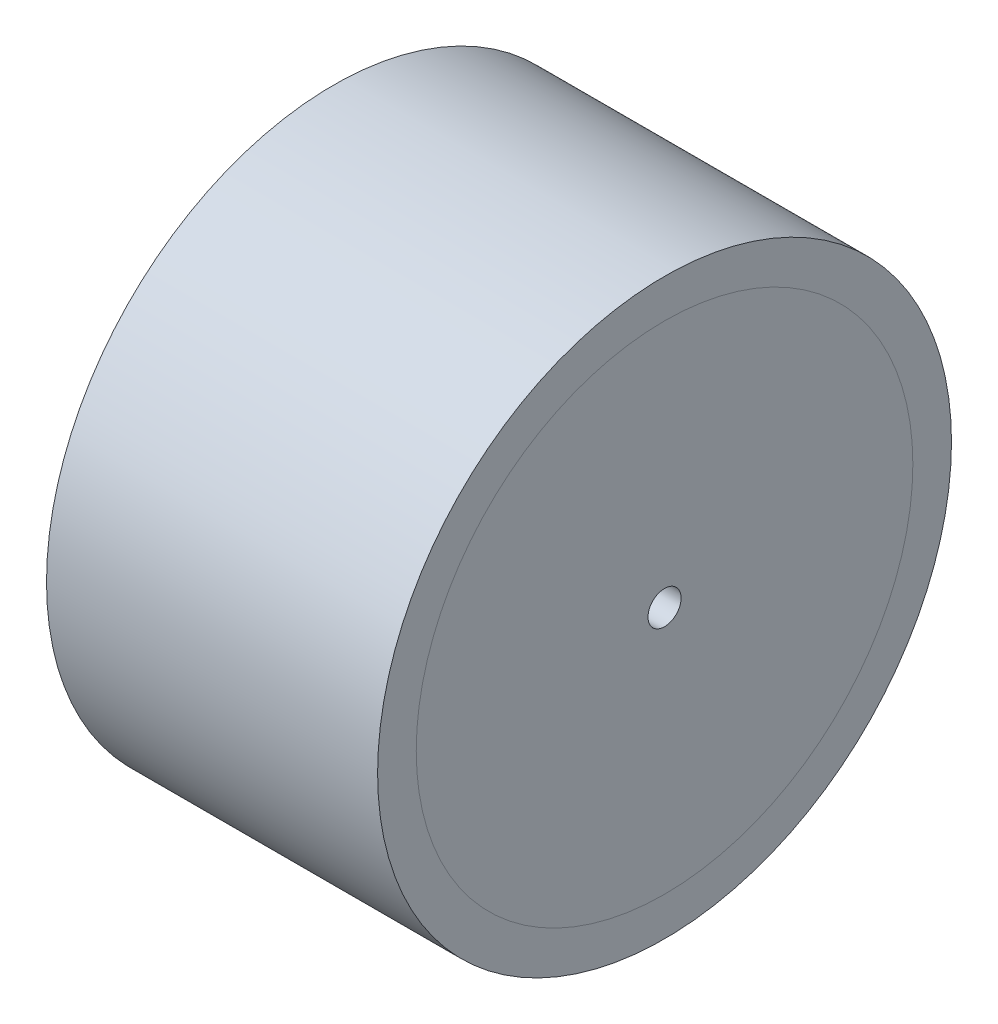
SolidWorks part; units mm, degrees
ref_plane "Front Plane" through (0, 0, 0) normal (0, 0, 1) x (1, 0, 0)
ref_plane "Top Plane" through (0, 0, 0) normal (0, 1, 0) x (1, 0, 0)
ref_plane "Right Plane" through (0, 0, 0) normal (1, 0, 0) x (0, 0, -1)
sketch "Sketch1" plane through (0, 0, 0) normal (1, 0, 0) x (0, 0, -1)
  circle A0 centre (0, 0) radius 26
  circle A1 centre (0, 0) radius 22.5
  dimension "D1" = 52
  dimension "D2" = 45
extrude "Boss-Extrude1" add sketch "Sketch1" along normal blind 30 contours A1 | A0 A1 region at (0, 0, 25.2646) region at (0, 0, 0)
split line "Split Line1"
sketch "Sketch1<4>" plane through (0, 0, 0) normal (1, 0, 0) x (0, 0, -1) same geometry as "Sketch1"
sketch "Sketch2" plane through (0, 0, 0) normal (-1, 0, 0) x (0, 0, 1)
  circle A0 centre (0, 0) radius 1.5
  dimension "D1" = 3
extrude "Cut-Extrude1" cut sketch "Sketch2" against normal through all
